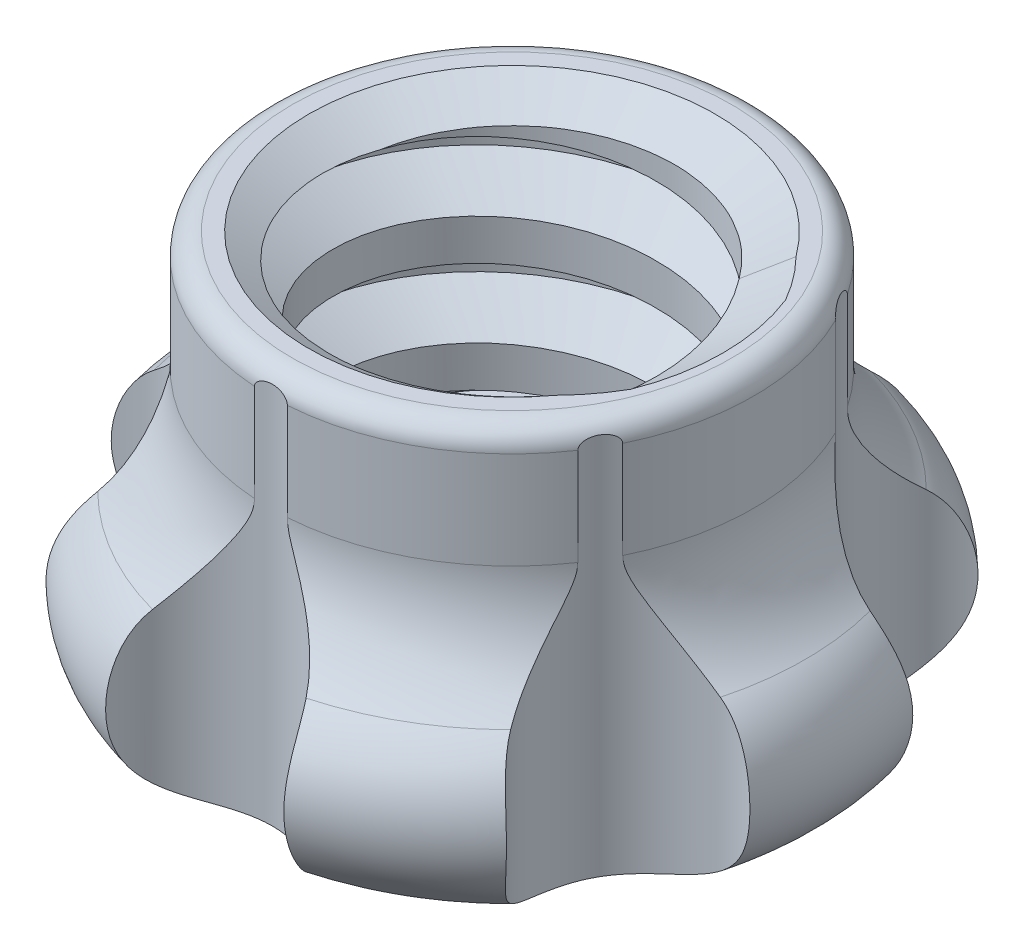
SolidWorks part; units mm, degrees
ref_plane "Front Plane" through (0, 0, 0) normal (0, 0, 1) x (1, 0, 0)
ref_plane "Top Plane" through (0, 0, 0) normal (0, 1, 0) x (1, 0, 0)
ref_plane "Right Plane" through (0, 0, 0) normal (1, 0, 0) x (0, 0, -1)
sketch "Sketch1" plane through (0, 0, 0) normal (0, 0, 1) x (1, 0, 0)
  line L0 (0, 18) -> (0, 0)
  line L1 (0, 0) -> (-10.6453, 0)
  line L2 (-11, 12.5788) -> (-11, 17)
  line L3 (-10, 18) -> (0, 18)
  line L4 (-15, 11.7316) -> (-15, -2.5725) construction
  arc A0 (-10.6453, 0) -> (-13.3339, 7.7803) centre (-10.6453, 4.3547) cw
  arc A1 (-13.3339, 7.7803) -> (-11, 12.5788) centre (-17.0999, 12.5788) ccw
  arc A2 (-11, 17) -> (-10, 18) centre (-10, 17) cw
  point P13 (-11, 18)
  dimension "D1" = 15
  dimension "D4" = 1
  dimension "D2" = 11
  dimension "D3" = 18
revolve "Revolve1" add sketch "Sketch1" angle 360 about L0
sketch "Sketch2" plane through (0, 0, 0) normal (0, -1, 0) x (1, 0, 0)
  circle A0 centre (0, 15) radius 4.0945
  circle A1 centre (0, 0) radius 15 construction
  circle A2 centre (12.9904, 7.5) radius 4.0945
  circle A3 centre (12.9904, -7.5) radius 4.0945
  circle A4 centre (0, -15) radius 4.0945
  circle A5 centre (-12.9904, -7.5) radius 4.0945
  circle A6 centre (-12.9904, 7.5) radius 4.0945
  dimension "D1" = 6
extrude "Cut-Extrude1" cut sketch "Sketch2" against normal through all
sketch "Sketch3" plane through (0, 0, 0) normal (0, -1, 0) x (1, 0, 0)
  circle A0 centre (0, 0) radius 5
  dimension "D1" = 10
extrude "Cut-Extrude2" cut sketch "Sketch3" against normal through all
sketch "Sketch4" plane through (0, 18, 0) normal (0, 1, 0) x (1, 0, 0)
  circle A0 centre (0, 0) radius 9.6
  dimension "D1" = 19.2
extrude "Cut-Extrude3" cut sketch "Sketch4" against normal blind 13
ref_plane "Plane1" through (0, 23, 0) normal (0, 1, 0) x (1, 0, 0)
sketch "Sketch5" plane through (0, 23, 0) normal (0, 1, 0) x (1, 0, 0)
  circle A0 centre (0, 0) radius 9.6 construction
  circle A1 centre (0, 0) radius 9.6
curve "Helix/Spiral1" pitch 5 height 20.5 turns 4.1
sketch "Sketch6" plane through (0, 0, 0) normal (0, 0, 1) x (1, 0, 0)
  line L0 (-7.4, 23) -> (-9.6, 23) construction
  line L1 (-7.4, 23.9298) -> (-7.4, 22.0702)
  line L2 (-7.4, 22.0702) -> (-9.6, 20.8)
  line L3 (-9.6, 20.8) -> (-9.6, 25.2)
  line L4 (-7.4, 23.9298) -> (-9.6, 25.2)
  spline S1 degree 3 poles (-9.6, 23) (-9.6, 22.8956) (-9.0908, 22.6843) (-6.9176, 22.3693) (-3.672, 22.0538) (0.1429, 21.7385) (3.9356, 21.4231) (7.1182, 21.1077) (9.1972, 20.7923) (9.8505, 20.4769) (8.9766, 20.1615) (6.7112, 19.8462) (3.4053, 19.5308) (-0.4285, 19.2154) (-4.1959, 18.9) (-7.3128, 18.5846) (-9.296, 18.2692) (-9.8381, 17.9538) (-8.855, 17.6385) (-6.4991, 17.3231) (-3.1357, 17.0077) (0.7138, 16.6923) (4.4527, 16.3769) (7.5012, 16.0615) (9.3869, 15.7462) (9.8174, 15.4308) (8.7258, 15.1154) (6.2816, 14.8) (2.8635, 14.4846) (-0.9985, 14.1692) (-4.7057, 13.8538) (-7.6834, 13.5385) (-9.4699, 13.2231) (-9.7884, 12.9077) (-8.5894, 12.5923) (-6.0588, 12.2769) (-2.5889, 11.9615) (1.2824, 11.6462) (4.9548, 11.3308) (7.8591, 11.0154) (9.545, 10.7) (9.7512, 10.3846) (8.4457, 10.0692) (5.8309, 9.7538) (2.3121, 9.4385) (-1.5651, 9.1231) (-5.1997, 8.8077) (-8.0282, 8.4923) (-9.6121, 8.1769) (-9.7058, 7.8615) (-8.2949, 7.5462) (-5.5981, 7.2308) (-2.0334, 6.9154) (1.8466, 6.6) (5.4402, 6.2846) (8.1905, 5.9692) (9.671, 5.6538) (9.6523, 5.3385) (8.1372, 5.0231) (5.3606, 4.7077) (1.7529, 4.3923) (-2.1265, 4.0769) (-5.6762, 3.7615) (-8.3461, 3.4462) (-9.7213, 3.1307) (-9.5928, 2.8157) (-8.5072, 2.6044) (-7.7666, 2.5) knots 0 0 0 0 0.015385 0.030769 0.046154 0.061538 0.076923 0.092308 0.107692 0.123077 0.138462 0.153846 0.169231 0.184615 0.2 0.215385 0.230769 0.246154 0.261538 0.276923 0.292308 0.307692 0.323077 0.338462 0.353846 0.369231 0.384615 0.4 0.415385 0.430769 0.446154 0.461538 0.476923 0.492308 0.507692 0.523077 0.538462 0.553846 0.569231 0.584615 0.6 0.615385 0.630769 0.646154 0.661538 0.676923 0.692308 0.707692 0.723077 0.738462 0.753846 0.769231 0.784615 0.8 0.815385 0.830769 0.846154 0.861538 0.876923 0.892308 0.907692 0.923077 0.938462 0.953846 0.969231 0.984615 1 1 1 1 construction
  point P3 (0, 0)
  point P4 (0, 0)
  point P9 (0, 0)
  dimension "D1" = 2.2
  dimension "D2" = 4.4
  dimension "D3" = 60
sweep "Sweep1" add profiles "Sketch6" path "Helix/Spiral1"
sketch "Sketch7" plane through (0, 18, 0) normal (0, 1, 0) x (1, 0, 0)
  circle A0 centre (0, 0) radius 11
extrude "Cut-Extrude4" cut sketch "Sketch7" along normal blind 10
sketch "Sketch8" plane through (0, 18, 0) normal (0, 1, 0) x (1, 0, 0)
  circle A0 centre (0, 0) radius 9.25
extrude "Cut-Extrude5" cut sketch "Sketch8" against normal blind 3 draft 60
sketch "Sketch9" plane through (0, 5, 0) normal (0, 1, 0) x (1, 0, 0)
  circle A0 centre (0, 0) radius 6.5
  dimension "D1" = 13
extrude "Cut-Extrude6" cut sketch "Sketch9" against normal up to surface (5 mm away) draft 10
fillet "Fillet1" radius 0.5 1 edges at (5.6184, 0, 0)
